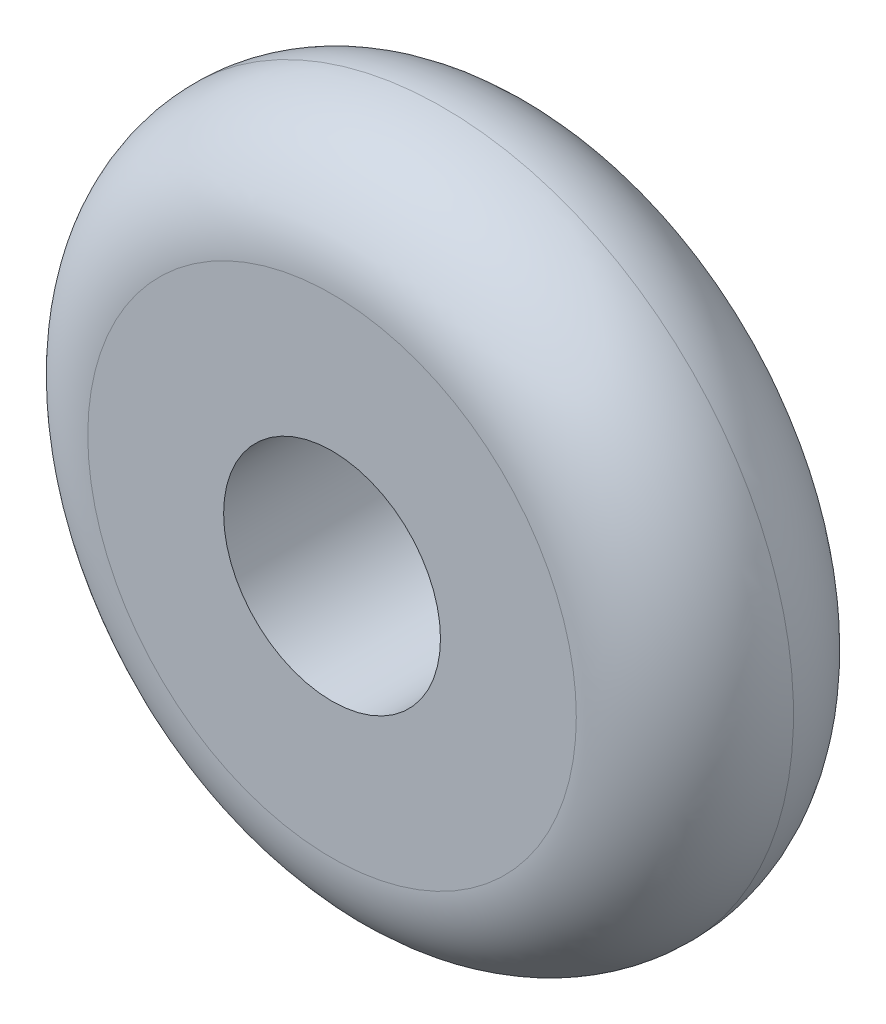
SolidWorks part; units mm, degrees
ref_plane "Front Plane" through (0, 0, 0) normal (0, 0, 1) x (1, 0, 0)
ref_plane "Top Plane" through (0, 0, 0) normal (0, 1, 0) x (1, 0, 0)
ref_plane "Right Plane" through (0, 0, 0) normal (1, 0, 0) x (0, 0, -1)
sketch "Sketch1" plane through (0, 0, 0) normal (0, 0, 1) x (1, 0, 0)
  circle A0 centre (0, 0) radius 34.75
  circle A1 centre (0, 0) radius 10.75
  dimension "D1" = 69.5
  dimension "D2" = 21.5
extrude "Boss-Extrude1" add sketch "Sketch1" along normal blind 22
sketch "Sketch2" plane through (0, 0, 0) normal (0, 1, 0) x (1, 0, 0)
  line L0 (-34.75, -11) -> (34.75, -11) construction
  line L1 (-34.75, 0) -> (-34.75, -22) construction
  line L2 (34.75, -22) -> (34.75, 0) construction
  line L3 (-34.75, -22) -> (34.75, -22) construction
  line L4 (0, 0) -> (0, -22) construction
  line L5 (-24.118, 0) -> (24.118, 0)
  line L6 (-24.118, -22) -> (24.118, -22)
  line L7 (24.118, -22) -> (34.75, -22)
  line L8 (34.75, -22) -> (34.75, -11)
  line L9 (34.75, -11) -> (37, 0)
  line L10 (37, 0) -> (24.118, 0)
  spline S0 degree 3 poles (34.75, -11) (34.75, -16.9631) (29.8423, -22.0292) (24.118, -22) knots 0 0 0 0 1 1 1 1
  spline S1 degree 3 poles (34.75, -11) (34.75, -5.0369) (29.8423, 0.0292) (24.118, 0) knots 0 0 0 0 1 1 1 1
revolve "Cut-Revolve1" cut sketch "Sketch2" angle 360 about L4 region at (32.3608, 0, 19.5171) region at (33.3839, 0, 2.8687)
